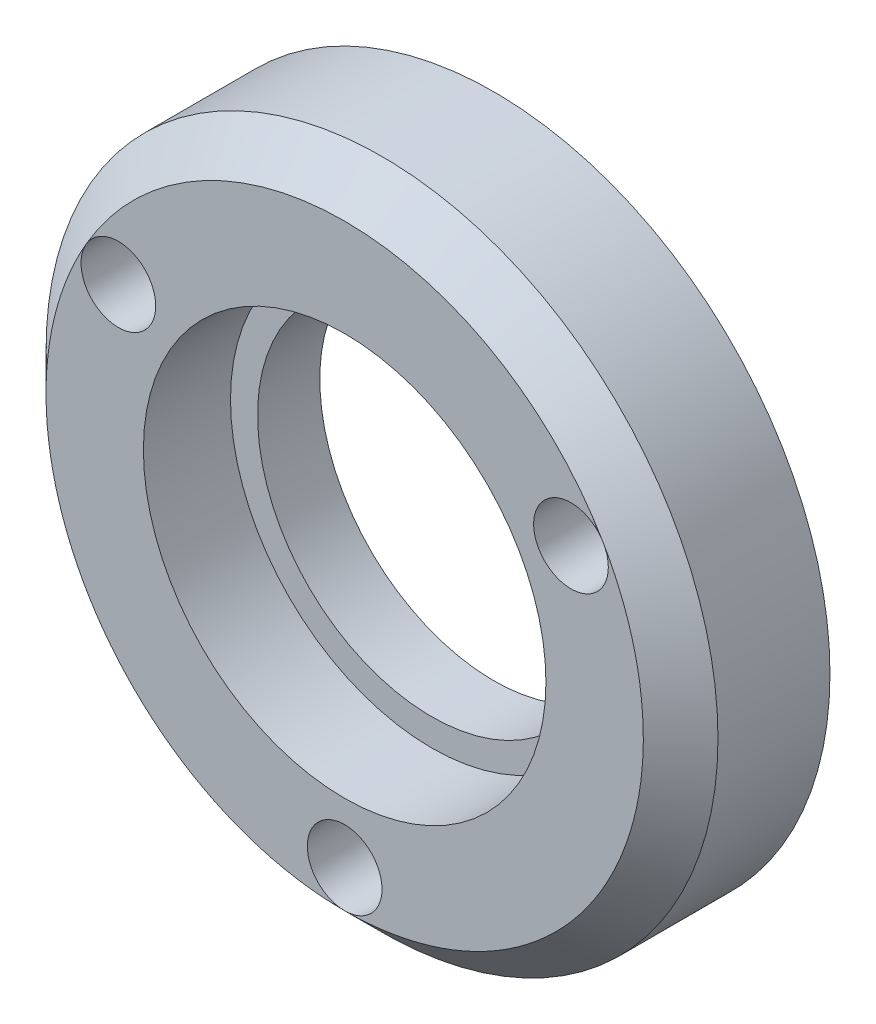
SolidWorks part; units mm, degrees
ref_plane "Спереди" through (0, 0, 0) normal (0, 0, 1) x (1, 0, 0)
ref_plane "Сверху" through (0, 0, 0) normal (0, 1, 0) x (1, 0, 0)
ref_plane "Справа" through (0, 0, 0) normal (1, 0, 0) x (0, 0, -1)
sketch "Эскиз1" plane through (0, 0, 0) normal (0, 0, 1) x (1, 0, 0)
  circle A0 centre (0, 0) radius 27
  dimension "D1" = 54
extrude "тело" add sketch "Эскиз1" along normal blind 12
sketch "Эскиз2" plane through (0, 0, 12) normal (0, 0, 1) x (1, 0, 0)
  circle A0 centre (0, 0) radius 16.175
  dimension "D1" = 32.35
extrude "углубление под подшипник" cut sketch "Эскиз2" against normal blind 7
sketch "Эскиз3" plane through (0, 0, 5) normal (0, 0, 1) x (1, 0, 0)
  circle A0 centre (0, 0) radius 14
  dimension "D1" = 28
extrude "сквозное отверстие" cut sketch "Эскиз3" against normal through all
sketch "Эскиз5" plane through (0, 0, 12) normal (0, 0, 1) x (1, 0, 0)
  line L0 (-18.1865, 10.5) -> (18.1865, 10.5) construction
  line L1 (-18.1865, 10.5) -> (0, 0) construction
  line L2 (0, 0) -> (18.1865, 10.5) construction
  circle A0 centre (0, 0) radius 21 construction
  circle A1 centre (-18.1865, 10.5) radius 1.65
  circle A3 centre (18.1865, 10.5) radius 1.65
  circle A4 centre (0, -21) radius 1.65
  dimension "D3" = 120
  dimension "D1" = 42
  dimension "D2" = 3.3
extrude "крепежные отверстия" cut sketch "Эскиз5" against normal through all
sketch "Эскиз6" plane through (0, 0, 12) normal (0, 0, 1) x (1, 0, 0)
  circle A0 centre (-18.1865, 10.5) radius 3
  circle A2 centre (18.1865, 10.5) radius 3
  circle A3 centre (0, -21) radius 3
  dimension "D1" = 6
extrude "отверстия под шляпки" cut sketch "Эскиз6" against normal blind 5
chamfer "Фаска1" distance 1.5 angle 45 3 edges at (1.65, -21, 7) (19.8365, 10.5, 7) (-16.5365, 10.5, 7)
chamfer "Фаска2" distance 3 angle 45 1 edges at (27, 0, 12)
sketch3d "Трехмерный эскиз1" [suppressed]
  line L0 (0, 0, 0) -> (-21.4087, 21.4087, 0) construction
sketch "Эскиз7" [suppressed] plane through (0, 0, 0) normal (0.7071, -0.7071, 0) x (0, 0, -1)
  line L0 (0, 2.5) -> (-3, 2.5)
  line L1 (0, 2.5) -> (0, -2.5)
  line L2 (0, -2.5) -> (-3, -2.5)
  arc A0 (-3, 2.5) -> (-3, -2.5) centre (-3, 0) ccw
  point P2 (0, 0)
  dimension "D1" = 2.5
  dimension "D2" = 3
extrude "Вырез-Вытянуть1" [suppressed] cut sketch "Эскиз7" against normal through all and the other way through all
sketch "Эскиз8" plane through (0, 0, 0) normal (0, 0, -1) x (-1, 0, 0)
  line L0 (0, 0) -> (0, 21) construction
  line L1 (0, 0) -> (-18.1865, -10.5) construction
  line L2 (0, 0) -> (18.1865, -10.5) construction
  circle A0 centre (0, 0) radius 21 construction
  circle A1 centre (0, 21) radius 3.65
  circle A2 centre (-18.1865, -10.5) radius 3.65
  circle A3 centre (18.1865, -10.5) radius 3.65
  dimension "D1" = 42
  dimension "D2" = 7.3
  dimension "D3" = 120
  dimension "D4" = 120
extrude "отверстия под шипы" cut sketch "Эскиз8" against normal blind 3
